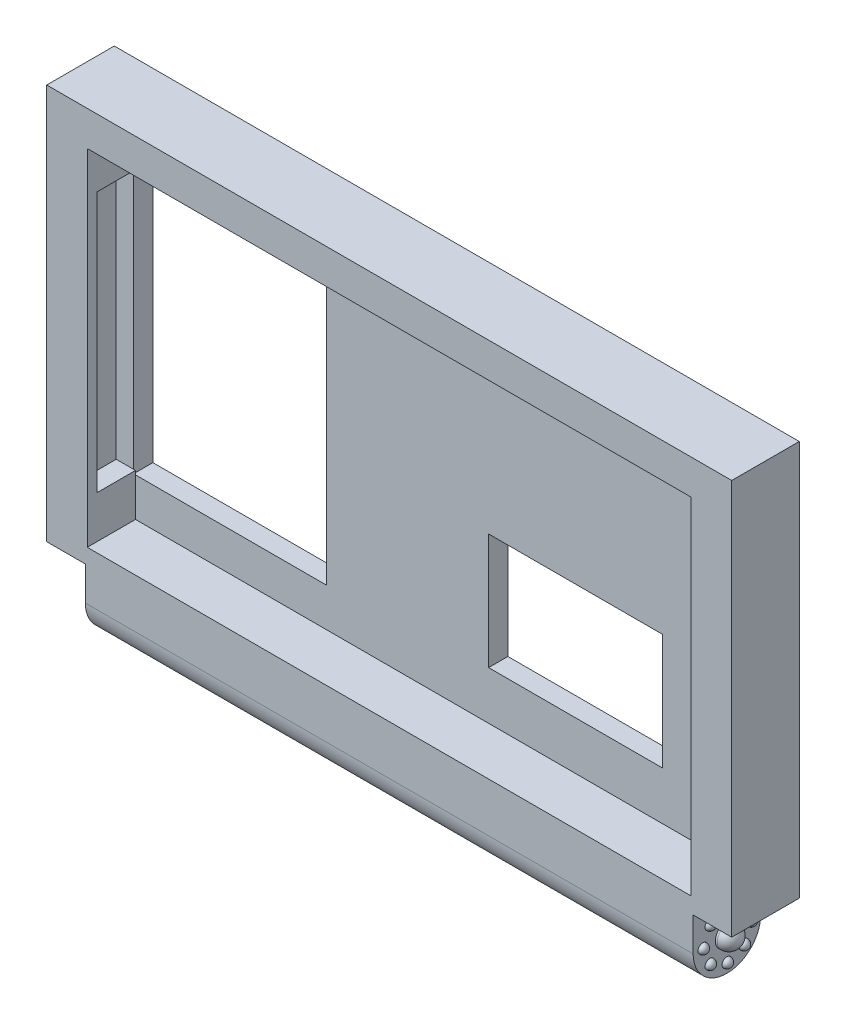
SolidWorks part; units mm, degrees
ref_plane "前视基准面" through (0, 0, 0) normal (0, 0, 1) x (1, 0, 0)
ref_plane "上视基准面" through (0, 0, 0) normal (0, 1, 0) x (1, 0, 0)
ref_plane "右视基准面" through (0, 0, 0) normal (1, 0, 0) x (0, 0, -1)
sketch "草图1" plane through (0, 0, 0) normal (0, 0, 1) x (1, 0, 0)
  line L1 (-17.75, 12) -> (17.75, 12)
  line L2 (-17.75, 12) -> (-17.75, -12)
  line L3 (-17.75, -12) -> (17.75, -12)
  line L4 (17.75, 12) -> (17.75, -12)
  line L5 (-17.75, 12) -> (17.75, -12) construction
  line L6 (-17.75, -12) -> (17.75, 12) construction
  point P0 (0, 0)
  dimension "D1" = 35.5
  dimension "D2" = 24
extrude "凸台-拉伸1" add sketch "草图1" along normal blind 3.5
sketch "草图2" plane through (0, 0, 3.5) normal (0, 0, 1) x (1, 0, 0)
  line L0 (-17.75, 12) -> (-17.75, -12) construction
  line L1 (-15.65, 10.2) -> (15.65, 10.2)
  line L2 (-15.65, 10.2) -> (-15.65, -7.7)
  line L3 (-15.65, -7.7) -> (15.65, -7.7)
  line L4 (15.65, 10.2) -> (15.65, -7.7)
  line L5 (17.75, -12) -> (17.75, 12) construction
  line L8 (17.75, 12) -> (-17.75, 12) construction
  dimension "D1" = 2.1
  dimension "D2" = 2.1
  dimension "D3" = 1.8
  dimension "D4" = 17.9
extrude "切除-拉伸1" cut sketch "草图2" against normal blind 2.5
sketch "草图12" plane through (-17.75, 0, 0) normal (-1, 0, 0) x (0, 0, 1)
  line L5 (3.5, 12) -> (3.5, -12) construction
  line L6 (0, -12) -> (3.5, -12)
  line L7 (0, -12) -> (0, -8.5)
  line L8 (0, -8.5) -> (3.5, -8.5)
  line L9 (3.5, -12) -> (3.5, -8.5)
  dimension "D1" = 3.5
  dimension "D2" = 3.5
extrude "切除-拉伸9" cut sketch "草图12" against normal blind 2
sketch "草图13" plane through (17.75, 0, 0) normal (1, 0, 0) x (0, 0, -1)
  line L0 (0, -12) -> (0, 12) construction
  line L1 (-3.5, -12) -> (0, -12)
  line L2 (-3.5, -12) -> (-3.5, -8.5)
  line L3 (-3.5, -8.5) -> (0, -8.5)
  line L4 (0, -12) -> (0, -8.5)
  dimension "D1" = 3.5
  dimension "D2" = 3.5
extrude "切除-拉伸10" cut sketch "草图13" against normal blind 2
sketch "草图14" plane through (0, 0, 1) normal (0, 0, 1) x (1, 0, 0)
  line L1 (-15.75, 8.2) -> (-5.75, 8.2)
  line L2 (-15.75, 8.2) -> (-15.75, -5.7)
  line L3 (-15.75, -5.7) -> (-5.75, -5.7)
  line L4 (-5.75, 8.2) -> (-5.75, -5.7)
  line L7 (15.65, 10.2) -> (-15.65, 10.2) construction
  line L8 (-15.65, -7.7) -> (15.65, -7.7) construction
  dimension "D1" = 10
  dimension "D2" = 2
  dimension "D3" = 2
extrude "切除-拉伸11" cut sketch "草图14" against normal blind 2
sketch "草图18" plane through (-15.65, 0, 0) normal (1, 0, 0) x (0, 0, -1)
  line L0 (-3.5, 10.2) -> (-3.5, -7.7) construction
  line L1 (-1, 8) -> (-3, 8)
  line L2 (-1, 8) -> (-1, -5.5)
  line L3 (-1, -5.5) -> (-3, -5.5)
  line L4 (-3, 8) -> (-3, -5.5)
  dimension "D1" = 2
  dimension "D2" = 0.5
  dimension "D3" = 13.5
extrude "切除-拉伸12" cut sketch "草图18" against normal blind 1
sketch "草图19" plane through (0, 0, 1) normal (0, 0, 1) x (1, 0, 0)
  line L0 (-15.65, -7.7) -> (15.65, -7.7) construction
  line L1 (2.65, 0.8) -> (11.65, 0.8)
  line L2 (2.65, 0.8) -> (2.65, -5.2)
  line L3 (2.65, -5.2) -> (11.65, -5.2)
  line L4 (11.65, 0.8) -> (11.65, -5.2)
  line L5 (15.65, -7.7) -> (15.65, 10.2) construction
  dimension "D1" = 6
  dimension "D2" = 2.5
  dimension "D3" = 9
  dimension "D4" = 4
extrude "切除-拉伸13" cut sketch "草图19" against normal blind 2
sketch "草图20" plane through (-15.75, 0, 0) normal (-1, 0, 0) x (0, 0, 1)
  line L0 (3.5, -12) -> (3.5, -8.5) construction
  line L3 (0, -12) -> (3.5, -12) construction
  circle A0 centre (1.75, -10.25) radius 0.6
  dimension "D1" = 1.2
  dimension "D3" = 1.75
  dimension "D2" = 1.75
extrude "凸台-拉伸3" add sketch "草图20" along normal blind 0.1
sketch "草图21" plane through (15.75, 0, 0) normal (1, 0, 0) x (0, 0, -1)
  line L0 (0, -12) -> (0, -8.5) construction
  line L2 (0, -8.5) -> (-3.5, -8.5) construction
  circle A0 centre (-1.75, -10.25) radius 0.6
  dimension "D1" = 1.2
  dimension "D2" = 1.75
  dimension "D3" = 1.75
extrude "凸台-拉伸4" add sketch "草图21" along normal blind 0.1
sketch "草图23" plane through (-15.85, 0, 0) normal (-1, 0, 0) x (0, 0, 1)
  line L0 (1.75, -9.65) -> (1.75, -10.85)
  circle A1 centre (1.75, -10.25) radius 0.6 construction
  circle A2 centre (1.75, -10.25) radius 0.6 construction
  arc A3 (1.75, -10.85) -> (1.75, -9.65) centre (1.75, -10.25) ccw
revolve "旋转1" add sketch "草图23" angle 360 about L0
sketch "草图24" plane through (15.85, 0, 0) normal (1, 0, 0) x (0, 0, -1)
  line L0 (-1.3595, -10.7055) -> (-2.1405, -9.7945)
  circle A5 centre (-1.75, -10.25) radius 0.6 construction
  circle A6 centre (-1.75, -10.25) radius 0.6 construction
  arc A7 (-2.1405, -9.7945) -> (-1.3595, -10.7055) centre (-1.75, -10.25) ccw
revolve "旋转2" add sketch "草图24" angle 360 about L0 region at (15.85, -10.4157, 1.9433)
fillet "圆角1" radius 1.75 1 edges at (0, -12, 3.5)
fillet "圆角2" radius 1.75 1 edges at (0, -12, 0)
sketch "草图25" plane through (15.75, 0, 0) normal (1, 0, 0) x (0, 0, -1)
  line L0 (-2, -9) -> (-1.5, -9)
  line L1 (0, -10.25) -> (0, -8.5) construction
  arc A9 (-2, -9) -> (-1.5, -9) centre (-1.75, -9) cw
  circle A10 centre (-1.75, -10.25) radius 0.6 construction
  point P23 (-1.75, -10.25)
  dimension "D1" = 0.5
  dimension "D2" = 0.25
  dimension "D3" = 1.25
  dimension "D4" = 1.75
revolve "旋转3" add sketch "草图25" angle 360 about L0
pattern_circular "阵列(圆周)2" count 8 over 360 about axis through (15.75, -10.25, 1.75) along (1, 0, 0) of "旋转3"
